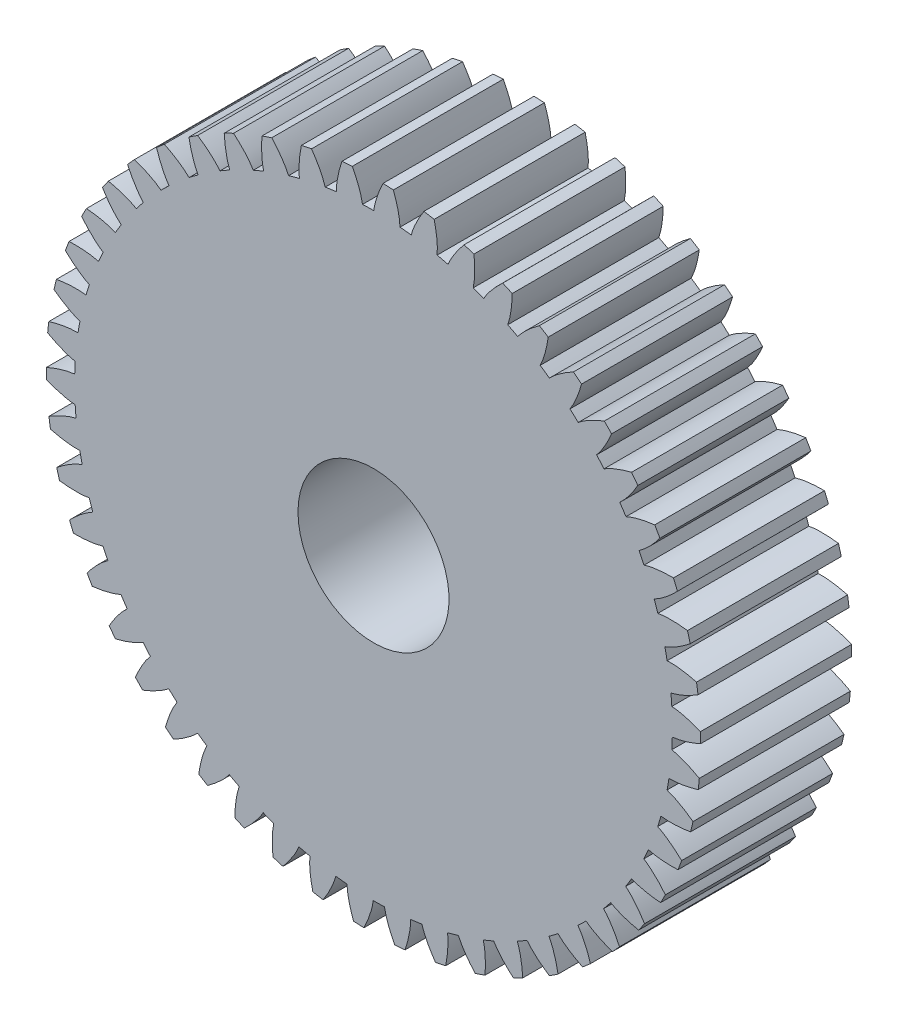
SolidWorks part; units mm, degrees
ref_plane "Front Plane" through (0, 0, 0) normal (0, 0, 1) x (1, 0, 0)
ref_plane "Top Plane" through (0, 0, 0) normal (0, 1, 0) x (1, 0, 0)
ref_plane "Right Plane" through (0, 0, 0) normal (1, 0, 0) x (0, 0, -1)
sketch "Involute Geometry" plane through (0, 0, 0) normal (0, 0, 1) x (1, 0, 0)
  line L0 (0, 23.4923) -> (0, 0) construction
  line L1 (0, 0) -> (1.1665, 25.9738) construction
  line L2 (2.1059, 23.3977) -> (0, 0) construction
  line L3 (0.3366, 24.9977) -> (0, 0) construction
  line L4 (0, 0) -> (1.9056, 24.9273) construction
  circle A1 centre (0, 0) radius 23.4923 construction
  circle A2 centre (0, 0) radius 25 construction
  circle A3 centre (0, 0) radius 26 construction
  circle A4 centre (0, 0) radius 23.75 construction
  arc A5 (0.7536, 25.9891) -> (1.5791, 25.952) centre (0, 0) cw
  arc A6 (0.3366, 24.9977) -> (1.9056, 24.9273) centre (0, 0) cw construction
  spline S0 degree 4 poles (0, 23.4923) (0, 23.5114) (0.0013, 23.5648) (0.0089, 23.6656) (0.0287, 23.8296) (0.081, 24.1325) (0.1926, 24.5862) (0.3554, 25.0766) (0.5626, 25.5852) (0.7677, 26.0245) (0.9438, 26.37) (1.171, 26.7822) (1.4642, 27.2682) (1.8332, 27.8211) (2.2875, 28.4323) (2.7797, 29.0321) (3.2982, 29.6089) (3.8411, 30.1634) (4.4053, 30.6951) (4.9175, 31.1416) (5.3665, 31.5096) (5.7503, 31.8087) (6.0572, 32.04) (6.3766, 32.2711) (6.6846, 32.4876) (7.0225, 32.7147) (7.3185, 32.909) (7.7622, 33.1868) (8.0307, 33.348) (8.4647, 33.6019) (8.6612, 33.7084) (8.8384, 33.8077) (8.891, 33.8352) (8.9294, 33.8561) (8.9501, 33.8675) knots 0 0 0 0 0 0.005377 0.015084 0.028532 0.04661 0.092111 0.146842 0.174209 0.201575 0.228941 0.256307 0.307035 0.361767 0.4165 0.471232 0.525964 0.580697 0.635429 0.690161 0.717528 0.744894 0.77226 0.799626 0.826992 0.854358 0.881725 0.909091 0.954545 0.977273 0.988636 0.994318 1 1 1 1 1 construction
  spline S1 degree 4 poles (0, 23.4923) (0, 23.5114) (0.0013, 23.5648) (0.0089, 23.6656) (0.0287, 23.8296) (0.081, 24.1325) (0.1926, 24.5862) (0.3554, 25.0766) (0.5626, 25.5852) (0.7677, 26.0245) (0.9438, 26.37) (1.171, 26.7822) (1.4642, 27.2682) (1.8332, 27.8211) (2.2875, 28.4323) (2.7797, 29.0321) (3.2982, 29.6089) (3.8411, 30.1634) (4.4053, 30.6951) (4.9175, 31.1416) (5.3665, 31.5096) (5.7503, 31.8087) (6.0572, 32.04) (6.3766, 32.2711) (6.6846, 32.4876) (7.0225, 32.7147) (7.3185, 32.909) (7.6041, 33.0878) (7.7558, 33.1811) (7.8311, 33.2268) knots 0 0 0 0 0 0.005377 0.015084 0.028532 0.04661 0.092111 0.146842 0.174209 0.201575 0.228941 0.256307 0.307035 0.361767 0.4165 0.471232 0.525964 0.580697 0.635429 0.690161 0.717528 0.744894 0.77226 0.799626 0.826992 0.854358 0.881725 0.909091 0.909091 0.909091 0.909091 0.909091
  spline S3 degree 4 poles (2.1059, 23.3977) (2.1076, 23.4167) (2.1111, 23.47) (2.1125, 23.5712) (2.1075, 23.7362) (2.0826, 24.0426) (2.0121, 24.5045) (1.8939, 25.0075) (1.7332, 25.5326) (1.5683, 25.9886) (1.4238, 26.3485) (1.2345, 26.7793) (0.9861, 27.2897) (0.6681, 27.8734) (0.2705, 28.5229) (-0.166, 29.1644) (-0.6307, 29.7854) (-1.1217, 30.3863) (-1.636, 30.9664) (-2.1061, 31.457) (-2.5203, 31.8638) (-2.8757, 32.1961) (-3.1606, 32.454) (-3.4581, 32.7128) (-3.7454, 32.9561) (-4.0616, 33.2125) (-4.339, 33.4325) (-4.756, 33.749) (-5.009, 33.9336) (-5.4185, 34.2255) (-5.6047, 34.3491) (-5.7723, 34.4639) (-5.8222, 34.4959) (-5.8585, 34.5202) (-5.8781, 34.5334) knots 0 0 0 0 0 0.005377 0.015084 0.028532 0.04661 0.092111 0.146842 0.174209 0.201575 0.228941 0.256307 0.307035 0.361767 0.4165 0.471232 0.525964 0.580697 0.635429 0.690161 0.717528 0.744894 0.77226 0.799626 0.826992 0.854358 0.881725 0.909091 0.954545 0.977273 0.988636 0.994318 1 1 1 1 1 construction
  spline S4 degree 4 poles (2.1059, 23.3977) (2.1076, 23.4167) (2.1111, 23.47) (2.1125, 23.5712) (2.1075, 23.7362) (2.0826, 24.0426) (2.0121, 24.5045) (1.8939, 25.0075) (1.7332, 25.5326) (1.5683, 25.9886) (1.4238, 26.3485) (1.2345, 26.7793) (0.9861, 27.2897) (0.6681, 27.8734) (0.2705, 28.5229) (-0.166, 29.1644) (-0.6307, 29.7854) (-1.1217, 30.3863) (-1.636, 30.9664) (-2.1061, 31.457) (-2.5203, 31.8638) (-2.8757, 32.1961) (-3.1606, 32.454) (-3.4581, 32.7128) (-3.7454, 32.9561) (-4.0616, 33.2125) (-4.339, 33.4325) (-4.6074, 33.6362) (-4.7502, 33.7427) (-4.8211, 33.795) knots 0 0 0 0 0 0.005377 0.015084 0.028532 0.04661 0.092111 0.146842 0.174209 0.201575 0.228941 0.256307 0.307035 0.361767 0.4165 0.471232 0.525964 0.580697 0.635429 0.690161 0.717528 0.744894 0.77226 0.799626 0.826992 0.854358 0.881725 0.909091 0.909091 0.909091 0.909091 0.909091
  dimension "D5" = 3.6
sketch "Sketch2" plane through (0, 0, 0) normal (0, 0, 1) x (1, 0, 0)
  circle A0 centre (0, 0) radius 23.75 construction
  circle A1 centre (0, 0) radius 23.75
extrude "Boss-Extrude1" add sketch "Sketch2" along normal mid plane 12
sketch "Sketch3" plane through (0, 0, 0) normal (0, 0, 1) x (1, 0, 0)
  arc A3 (0.0199, 23.75) -> (2.1092, 23.6562) centre (0, 0) cw
  arc A4 (1.5791, 25.952) -> (0.7536, 25.9891) centre (0, 0) ccw construction
  arc A5 (1.5791, 25.952) -> (0.7536, 25.9891) centre (0, 0) ccw
  circle A7 centre (0, 0) radius 23.75 construction
  spline S0 degree 4 poles (999.8204, 40.2462) (20.7121, 20.125) (0.4503, 21.1025) (-0.1347, 22.474) (0.0287, 23.8296) (0.081, 24.1325) (0.1926, 24.5862) (0.3554, 25.0766) (0.5626, 25.5852) (0.7677, 26.0245) (0.9438, 26.37) (1.171, 26.7822) (1.4642, 27.2682) (1.8332, 27.8211) (2.2875, 28.4323) (2.7797, 29.0321) (3.2982, 29.6089) (3.8411, 30.1634) (4.4053, 30.6951) (4.9175, 31.1416) (5.3665, 31.5096) (5.7503, 31.8087) (6.0572, 32.04) (6.3766, 32.2711) (6.6846, 32.4876) (7.0225, 32.7147) (8.3806, 33.6059) (11.7895, 35.5553) (-19.6779, 16.1915) (862.8738, 551.731) knots -0.338747 -0.338747 -0.338747 -0.338747 -0.338747 0.005377 0.015084 0.028532 0.04661 0.092111 0.146842 0.174209 0.201575 0.228941 0.256307 0.307035 0.361767 0.4165 0.471232 0.525964 0.580697 0.635429 0.690161 0.717528 0.744894 0.77226 0.799626 0.826992 0.854358 0.881725 1.301773 1.301773 1.301773 1.301773 1.301773 only from (0, 23.4923) to (7.5082, 22.3415) construction
  spline S1 degree 4 poles (0.0199, 23.75) (0.0244, 23.7861) (0.0384, 23.8856) (0.0837, 24.1434) (0.1926, 24.5862) (0.3677, 25.1136) (0.5556, 25.5675) (0.6944, 25.8667) (0.7536, 25.9891) knots 0.018251 0.018251 0.018251 0.018251 0.018251 0.028532 0.04661 0.092111 0.146842 0.185208 0.185208 0.185208 0.185208 0.185208
  spline S3 degree 4 poles (-992.1874, 129.7099) (-18.8247, 21.9006) (1.4432, 21.0579) (2.1488, 22.3715) (2.1075, 23.7362) (2.0826, 24.0426) (2.0121, 24.5045) (1.8939, 25.0075) (1.7332, 25.5326) (1.5683, 25.9886) (1.4238, 26.3485) (1.2345, 26.7793) (0.9861, 27.2897) (0.6681, 27.8734) (0.2705, 28.5229) (-0.166, 29.1644) (-0.6307, 29.7854) (-1.1217, 30.3863) (-1.636, 30.9664) (-2.1061, 31.457) (-2.5203, 31.8638) (-2.8757, 32.1961) (-3.1606, 32.454) (-3.4581, 32.7128) (-3.7454, 32.9561) (-4.0616, 33.2125) (-5.3344, 34.2219) (-8.5548, 36.469) (21.0501, 14.3623) (-809.9417, 626.8594) knots -0.338747 -0.338747 -0.338747 -0.338747 -0.338747 0.005377 0.015084 0.028532 0.04661 0.092111 0.146842 0.174209 0.201575 0.228941 0.256307 0.307035 0.361767 0.4165 0.471232 0.525964 0.580697 0.635429 0.690161 0.717528 0.744894 0.77226 0.799626 0.826992 0.854358 0.881725 1.301773 1.301773 1.301773 1.301773 1.301773 only from (2.1059, 23.3977) to (-4.8211, 33.795) construction
  spline S4 degree 4 poles (2.1092, 23.6562) (2.1079, 23.6925) (2.1029, 23.7929) (2.0809, 24.0537) (2.0121, 24.5045) (1.885, 25.0455) (1.7385, 25.5144) (1.6271, 25.8248) (1.5791, 25.952) knots 0.018251 0.018251 0.018251 0.018251 0.018251 0.028532 0.04661 0.092111 0.146842 0.185208 0.185208 0.185208 0.185208 0.185208
extrude "Boss-Extrude2" add sketch "Sketch3" along normal through all and the other way through all
fillet "Fillet2" [suppressed] radius 0.381
pattern_circular "CirPattern1" count 50 over 360 about axis through (0, 0, 6) along (0, 0, -1) of "Boss-Extrude2", "Fillet2"
ref_axis "Axis1" through (0, 0, 6) along (0, 0, -1)
sketch "Sketch4" plane through (0, 0, -6) normal (0, 0, -1) x (-1, 0, 0)
  circle A1 centre (0, 0) radius 6
  dimension "D1" = 12
extrude "Cut-Extrude1" cut sketch "Sketch4" against normal through all
equation "\"N\" = 50'Number of Teeth"
equation "\"m\"= 1mm'Diametral Pitch"
equation "\"phi\"= 20deg'Pressure Angle"
equation "\"a\"= \"m\"'Addendum"
equation "\"b\"= 1.25 * \"m\"'Dedendum"
equation "\"Dp\"= \"N\" * \"m\"'Pitch diameter"
equation "\"Db\"= \"Dp\" * cos ( \"phi\" )'Base diameter"
equation "\"D1@Involute Geometry\" = \"Db\""
equation "\"D2@Involute Geometry\" = \"Dp\""
equation "\"D3@Involute Geometry\" = \"Dp\" + 2 * \"a\""
equation "\"D4@Involute Geometry\" = \"Dp\" - 2 * \"b\""
equation "\"D1@CirPattern1\"=\"N\""
equation "\"D5@Involute Geometry\"=180/\"N\""
equation "\"D1@Boss-Extrude1\"=12*\"m\""
equation "\"alpha\"= sqr ( \"Dp\" ^ 2 - \"Db\" ^ 2 ) / \"Db\" * 180 / pi - \"phi\""
equation "\"beta\"= ( ( 360deg / \"N\" ) / 4 - \"alpha\" )"
